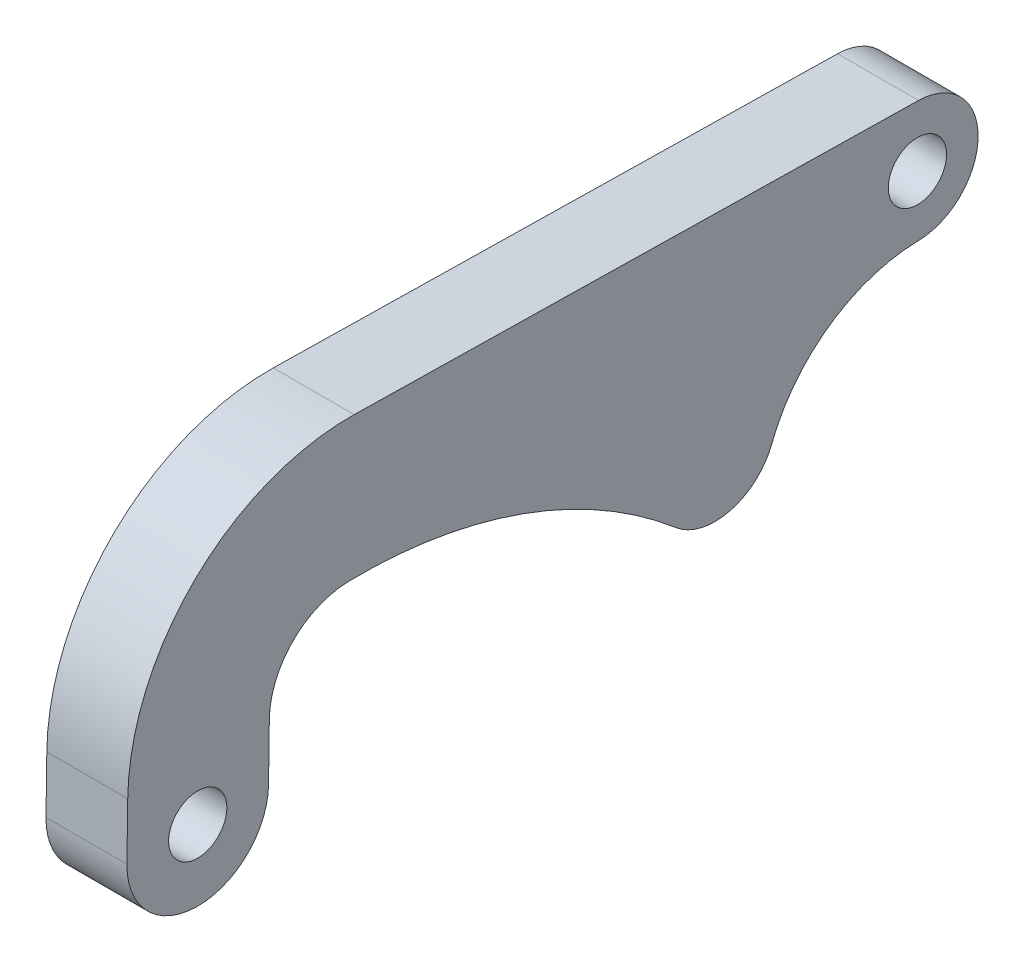
SolidWorks part; units mm, degrees
ref_plane "Front Plane" through (0, 0, 0) normal (0, 0, 1) x (1, 0, 0)
ref_plane "Top Plane" through (0, 0, 0) normal (0, 1, 0) x (1, 0, 0)
ref_plane "Right Plane" through (0, 0, 0) normal (1, 0, 0) x (0, 0, -1)
sketch "Sketch1" plane through (0, 0, 0) normal (1, 0, 0) x (0, 0, -1)
  line L0 (0, 0) -> (56.4713, 16.1581) construction
  line L1 (56.4713, 16.1581) -> (36.2438, 16.1581) construction
  line L2 (-5.5557, 0.0789) -> (-5.4929, 4.4978)
  line L3 (5.5557, -0.0789) -> (5.6184, 4.3401)
  line L4 (56.5563, 20.9198) -> (12.2792, 21.7097)
  line L5 (11.8545, 10.5989) -> (56.5563, 11.3963) construction
  line L6 (36.2438, 11.034) -> (36.2438, 21.2822) construction
  circle A0 centre (0, 0) radius 2.286
  circle A1 centre (56.4713, 16.1581) radius 2.286
  arc A2 (11.8545, 10.5989) -> (5.6184, 4.3401) centre (11.9678, 4.2499) ccw
  arc A3 (-5.5557, 0.0789) -> (5.5557, -0.0789) centre (0, 0) ccw
  arc A4 (56.5563, 11.3963) -> (56.5563, 20.9198) centre (56.4713, 16.1581) ccw
  arc A5 (-5.4929, 4.4978) -> (12.2792, 21.7097) centre (11.9678, 4.2499) cw
  arc A6 (11.8545, 10.5989) -> (37.5097, 1.4187) centre (12.5416, -27.9191) cw
  arc A7 (37.5097, 1.4187) -> (45.0414, 3.3359) centre (40.5963, 5.0456) ccw
  arc A8 (45.0414, 3.3359) -> (56.5563, 11.3963) centre (56.7806, -1.1793) cw
  point P5 (36.2438, 16.1581)
  dimension "D1" = 0.7937
  dimension "D2" = 4.572
  dimension "D3" = 12.7
  dimension "D4" = 9.525
  dimension "D5" = 11.1125
  dimension "D6" = 58.7375
  dimension "D7" = 15.875
  dimension "D9" = 4.7625
  dimension "D11" = 11.1125
  dimension "D8" = 11.1125
  dimension "D10" = 12.7
extrude "Boss-Extrude1" add sketch "Sketch1" along normal mid plane 6.35
